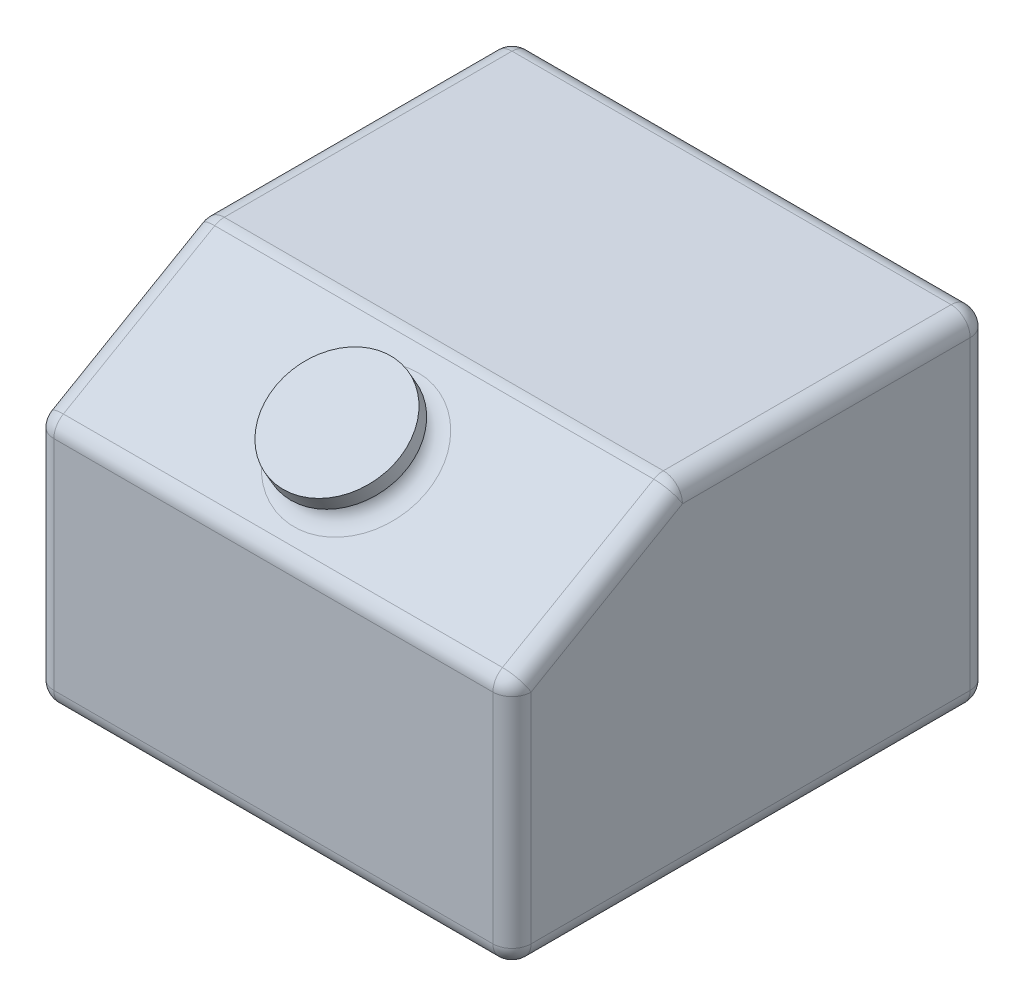
SolidWorks part; units mm, degrees
ref_plane "정면" through (0, 0, 0) normal (0, 0, 1) x (1, 0, 0)
ref_plane "윗면" through (0, 0, 0) normal (0, 1, 0) x (1, 0, 0)
ref_plane "우측면" through (0, 0, 0) normal (1, 0, 0) x (0, 0, -1)
sketch "스케치1" plane through (0, 0, 0) normal (0, 1, 0) x (1, 0, 0)
  line L1 (0, 0) -> (250, 0)
  line L2 (0, 0) -> (0, 250)
  line L3 (0, 250) -> (250, 250)
  line L4 (250, 0) -> (250, 250)
  dimension "D1" = 250
  dimension "D2" = 250
extrude "보스-돌출1" add sketch "스케치1" along normal blind 180
chamfer "모따기1" distance 50 angle 60 1 edges at (125, 180, 0) first distance on face at (125, 90, 0)
sketch "스케치2" plane through (0, 97.5, 56.2917) normal (0, 0.866, 0.5) x (1, 0, 0)
  line L0 (125, 325.5953) -> (125, -95.5953) construction
  line L1 (-60.6396, 115) -> (310.6396, 115) construction
  line L2 (250, 165) -> (250, 65) construction
  line L3 (250, 65) -> (0, 65) construction
  circle A0 centre (125, 115) radius 32.5
  circle A1 centre (125, 115) radius 27.5
  point P4 (125, 115)
  point P7 (250, 115)
  point P9 (125, 115)
  point P13 (125, 65)
  dimension "D1" = 65
  dimension "D2" = 55
extrude "보스-돌출2" add sketch "스케치2" along normal blind 20 contours A1 region at (125, 155, -43.3013)
extrude "보스-돌출3" add sketch "스케치2<3>" against normal blind 8 from offset 20
sketch "스케치2<3>" plane through (0, 97.5, 56.2917) normal (0, 0.866, 0.5) x (1, 0, 0) same geometry as "스케치2"
fillet "필렛1" radius 10 16 edges at (125, 141.25, -19.4856) (125, 180, -86.6025) (0, 180, -168.3013) (0, 155, -43.3013) (125, 180, -250) (0, 90, -250) (250, 90, -250) (250, 155, -43.3013) (250, 180, -168.3013) (0, 65, 0) (125, 130, 0) (250, 65, 0) (125, 0, 0) (250, 0, -125) (125, 0, -250) (0, 0, -125)
sketch "스케치3" plane through (250, 0, 0) normal (1, 0, 0) x (0, 0, -1)
  line L10 (237, 13) -> (237, 167)
  line L11 (237, 167) -> (90.0859, 167)
  line L12 (90.0859, 167) -> (13, 122.4944)
  line L13 (13, 122.4944) -> (13, 13)
  line L14 (13, 13) -> (237, 13)
  line L15 (237, 13) -> (237, 167)
  line L16 (237, 167) -> (90.0859, 167)
  line L17 (90.0859, 167) -> (13, 122.4944)
  line L18 (13, 122.4944) -> (13, 13)
  line L19 (13, 13) -> (237, 13)
  dimension "D1" = 3
extrude "컷-돌출1" cut sketch "스케치3" against normal blind 230 from offset 10 offset against normal yes
